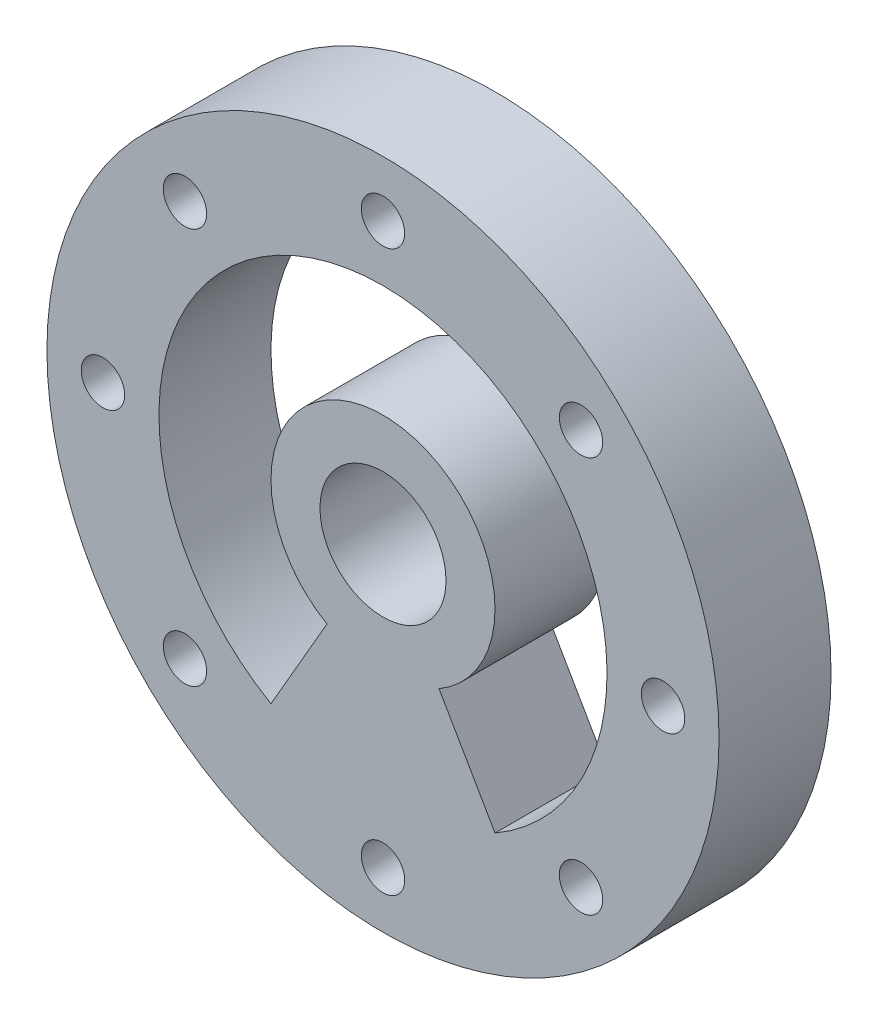
SolidWorks part; units mm, degrees
ref_plane "Front Plane" through (0, 0, 0) normal (0, 0, 1) x (1, 0, 0)
ref_plane "Top Plane" through (0, 0, 0) normal (0, 1, 0) x (1, 0, 0)
ref_plane "Right Plane" through (0, 0, 0) normal (1, 0, 0) x (0, 0, -1)
ref_axis "Axis1" through (0, 0, 5.5) along (0, 0, -1)
sketch "Sketch4" plane through (0, 0, 0) normal (0, 0, 1) x (1, 0, 0)
  line L0 (0, 0) -> (-9.5, -16.4545) construction
  line L1 (0, 0) -> (9.5, -16.4545) construction
  line L2 (-4, -6.9282) -> (-8, -13.8564)
  line L3 (4, -6.9282) -> (8, -13.8564)
  arc A1 (8, -13.8564) -> (-8, -13.8564) centre (0, 0) ccw
  arc A2 (4, -6.9282) -> (-4, -6.9282) centre (0, 0) ccw
sketch "Sketch6" plane through (0, 0, 0) normal (0, 0, 1) x (1, 0, 0)
  circle A0 centre (0, 0) radius 24
extrude "Boss-Extrude1" add sketch "Sketch6" along normal blind 8
extrude "Cut-Extrude4" cut sketch "Sketch4" along normal blind 8
sketch "Sketch7" plane through (0, 0, 0) normal (0, 0, -1) x (-1, 0, 0)
  circle A0 centre (0, 0) radius 4.5
extrude "Cut-Extrude5" cut sketch "Sketch7" against normal up to surface (8 mm away) up to face at (24, 0, 8)
sketch "Sketch8" plane through (0, 0, 8) normal (0, 0, -1) x (-1, 0, 0)
  line L0 (0, 0) -> (0, 20) construction
  circle A0 centre (0, 20) radius 1.55
  circle A1 centre (14.1421, 14.1421) radius 1.55
  circle A2 centre (20, 0) radius 1.55
  circle A3 centre (14.1421, -14.1421) radius 1.55
  circle A4 centre (0, -20) radius 1.55
  circle A5 centre (-14.1421, -14.1421) radius 1.55
  circle A6 centre (-20, 0) radius 1.55
  circle A7 centre (-14.1421, 14.1421) radius 1.55
  point P20 (0, 0)
  dimension "D1" = 8
extrude "Cut-Extrude6" cut sketch "Sketch8" along normal up to surface (8 mm away) up to face at (-4.5, 0, 0)
